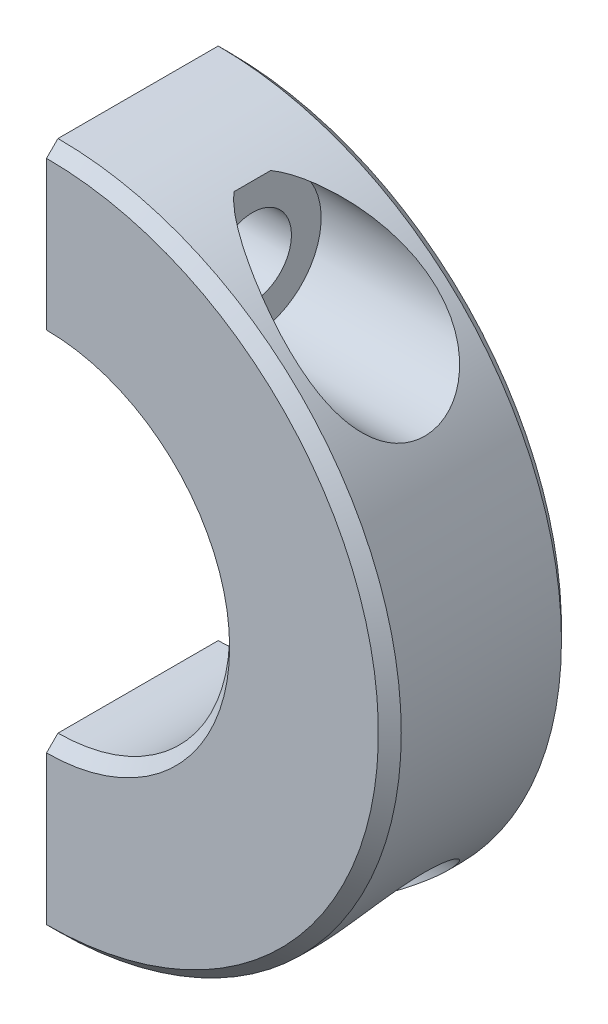
SolidWorks part; units mm, degrees
ref_plane "前视基准面" through (0, 0, 0) normal (0, 0, 1) x (1, 0, 0)
ref_plane "上视基准面" through (0, 0, 0) normal (0, 1, 0) x (1, 0, 0)
ref_plane "右视基准面" through (0, 0, 0) normal (1, 0, 0) x (0, 0, -1)
sketch "草图1" plane through (0, 0, 0) normal (0, 0, 1) x (1, 0, 0)
  line L0 (-7.8243, 23.0052) -> (-7.8243, 15.5052)
  line L1 (-7.8243, 0.5052) -> (-7.8243, -6.9948)
  arc A0 (-7.8243, -6.9948) -> (-7.8243, 23.0052) centre (-7.8243, 8.0052) ccw
  arc A1 (-7.8243, 0.5052) -> (-7.8243, 15.5052) centre (-7.8243, 8.0052) ccw
  dimension "D1" = 30
  dimension "D2" = 15
extrude "凸台-拉伸1" add sketch "草图1" along normal blind 8
sketch "草图2" plane through (-7.8243, 0, 0) normal (-1, 0, 0) x (0, 0, 1)
  circle A0 centre (4, 19.2552) radius 3
  circle A1 centre (4, 19.2552) radius 1.7
  dimension "D1" = 6
  dimension "D2" = 3.4
extrude "切除-拉伸1" cut sketch "草图2" against normal blind 10 from offset 5 contours A0 offset against normal yes
extrude "切除-拉伸2" cut sketch "草图2<3>" against normal blind 5 contours A1
sketch "草图2<3>" plane through (-7.8243, 0, 0) normal (-1, 0, 0) x (0, 0, 1) same geometry as "草图2"
sketch "草图3" plane through (-7.8243, 0, 0) normal (-1, 0, 0) x (0, 0, 1)
  circle A0 centre (4, -3.2448) radius 3
  circle A1 centre (4, -3.2448) radius 1.7
  dimension "D1" = 6
  dimension "D2" = 3.4
extrude "切除-拉伸4" cut sketch "草图3" against normal blind 5 contours A1
extrude "切除-拉伸3" cut sketch "草图3<3>" against normal blind 10 from offset 5 contours A0 offset against normal yes
sketch "草图3<3>" plane through (-7.8243, 0, 0) normal (-1, 0, 0) x (0, 0, 1) same geometry as "草图3"
chamfer "倒角1" distance 0.5 4 edges at (7.1757, 8.0052, 0) (7.1757, 8.0052, 8) (-0.3243, 8.0052, 0) (-0.3243, 8.0052, 8)
